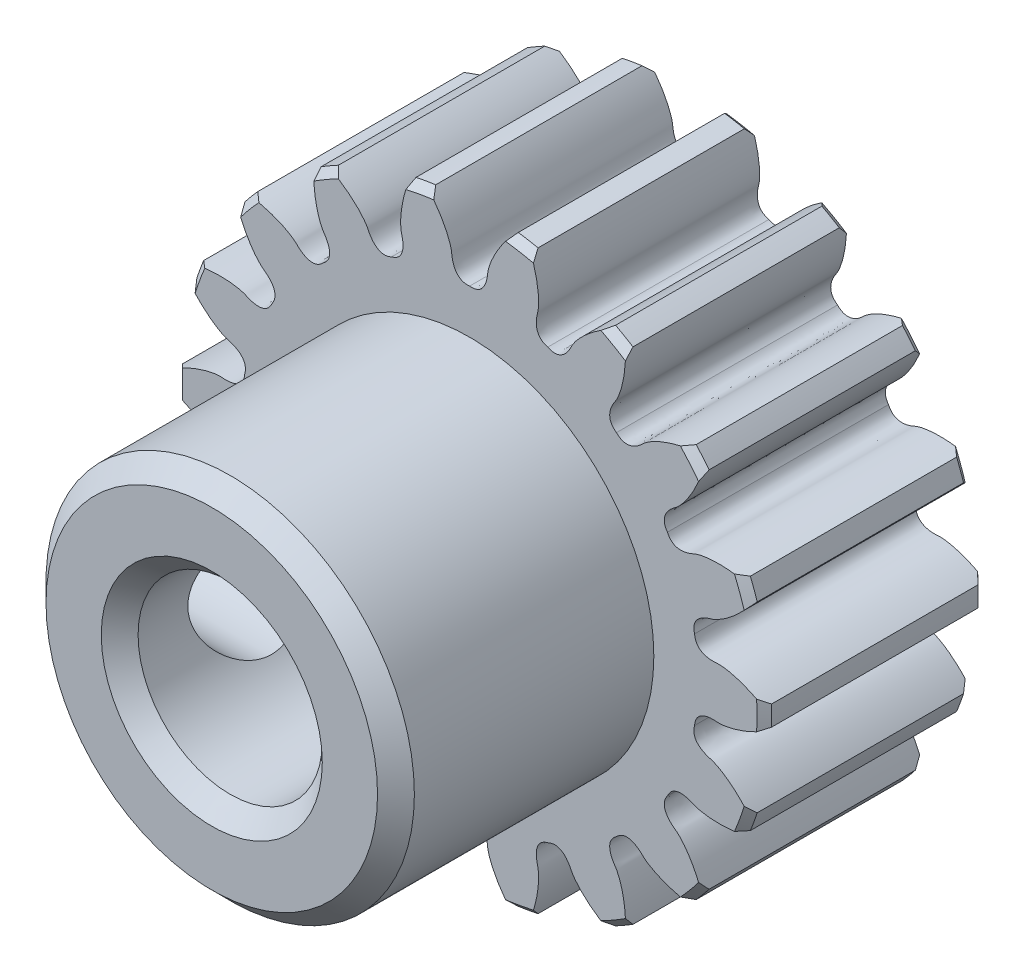
SolidWorks part; units mm, degrees
ref_plane "Front Plane" through (0, 0, 0) normal (0, 0, 1) x (1, 0, 0)
ref_plane "Top Plane" through (0, 0, 0) normal (0, 1, 0) x (1, 0, 0)
ref_plane "Right Plane" through (0, 0, 0) normal (1, 0, 0) x (0, 0, -1)
ref_axis "Ось вращения" through (0, 0, -4.277) along (0, 0, 1)
sketch "Gear-BaseSketch" plane through (0, 0, 0) normal (0, 0, 1) x (1, 0, 0)
  circle A0 centre (0, 0) radius 8
  dimension "D1" = 16
extrude "0.8 Module, 14,4000mm P.D." add sketch "Gear-BaseSketch" along normal mid plane 6
sketch "Tooth-Sketch; Backlash: 0,0000mm" plane through (0, 0, 0) normal (0, 0, 1) x (1, 0, 0)
  line L0 (0, 0) -> (0, 10.1487) construction
  arc A0 (-1.1887, 8.0004) -> (1.1887, 8.0004) centre (0, 0) cw
  spline S0 degree 3 poles (-1.1887, 8.0004) (-1.1086, 7.9105) (-0.9981, 7.7756) (-0.8682, 7.5934) (-0.7874, 7.4689) (-0.7187, 7.3521) (-0.6612, 7.2438) (-0.6139, 7.1448) (-0.5761, 7.0557) (-0.5467, 6.9771) (-0.5248, 6.9096) (-0.5092, 6.8537) (-0.499, 6.8097) (-0.4931, 6.7779) (-0.4902, 6.7588) (-0.4887, 6.7435) (-0.4868, 6.7196) (-0.4829, 6.6833) (-0.4745, 6.6262) (-0.4602, 6.5585) (-0.4361, 6.4818) (-0.4042, 6.4101) (-0.3617, 6.3426) (-0.3042, 6.2799) (-0.1904, 6.2022) (-0.0755, 6.1931) (0, 6.1994) knots 0 0 0 0 0.157962 0.228481 0.293358 0.352594 0.406188 0.454141 0.496452 0.533122 0.56415 0.589537 0.609282 0.623386 0.631848 0.634669 0.643503 0.663346 0.682539 0.719174 0.75397 0.787768 0.821855 0.858104 0.898741 1 1 1 1
  spline S1 degree 3 poles (1.1887, 8.0004) (1.1086, 7.9105) (0.9981, 7.7756) (0.8682, 7.5934) (0.7874, 7.4689) (0.7187, 7.3521) (0.6612, 7.2438) (0.6139, 7.1448) (0.5761, 7.0557) (0.5467, 6.9771) (0.5248, 6.9096) (0.5092, 6.8537) (0.499, 6.8097) (0.4931, 6.7779) (0.4902, 6.7588) (0.4887, 6.7435) (0.4868, 6.7196) (0.4829, 6.6833) (0.4745, 6.6262) (0.4602, 6.5585) (0.4361, 6.4818) (0.4042, 6.4101) (0.3617, 6.3426) (0.3042, 6.2799) (0.1904, 6.2022) (0.0755, 6.1931) (0, 6.1994) knots 0 0 0 0 0.157962 0.228481 0.293358 0.352594 0.406188 0.454141 0.496452 0.533122 0.56415 0.589537 0.609282 0.623386 0.631848 0.634669 0.643503 0.663346 0.682539 0.719174 0.75397 0.787768 0.821855 0.858104 0.898741 1 1 1 1
extrude "Tooth-Cut, Coarse Pitch Involute 20 deg" cut sketch "Tooth-Sketch; Backlash: 0,0000mm" against normal through all and the other way through all
chamfer "Фаска шестерни" distance 0.2 angle 45 2 edges at (0, -8, -3) (0, -8, 3)
pattern_circular "Tooth Pattern, 18 / 18" count 18 over 360 about axis through (0, 0, -4.277) along (0, 0, 1) of "Tooth-Cut, Coarse Pitch Involute 20 deg"
sketch "Sketch3" plane through (0, 0, 3) normal (0, 0, 1) x (1, 0, 0)
  circle A0 centre (0, 0) radius 5
  circle A1 centre (0, 0) radius 2.5
  dimension "D1" = 5
  dimension "D2" = 10
extrude "Хвостовик" add sketch "Sketch3" along normal blind 7
sketch "Sketch4" plane through (0, 0, -3) normal (0, 0, -1) x (-1, 0, 0)
  circle A0 centre (0, 0) radius 5
  dimension "D1" = 10
extrude "Вырез" cut sketch "Sketch4" against normal blind 3
sketch "Sketch5" plane through (0, 0, 3) normal (0, 0, 1) x (1, 0, 0)
  circle A0 centre (0, 0) radius 2.5
extrude "Сквозное" cut sketch "Sketch5" against normal blind 3
chamfer "Фаска" distance 0.5 angle 45 4 edges at (5, 0, 10) (2.5, 0, 10) (-5, 0, -3) (2.5, 0, 0)
ref_plane "Продольная" through (0, 0, 0) normal (1, 0, 0) x (0, 0, -1)
ref_plane "Касательная" through (-5, 0, 0) normal (-1, 0, 0) x (0, 0, 1)
sketch "Sketch6" plane through (-5, 0, 0) normal (-1, 0, 0) x (0, 0, 1)
  line L0 (-4.277, 0) -> (11.0141, 0) construction
  line L1 (10, -4.5) -> (10, 4.5) construction
  circle A0 centre (6.5, 0) radius 1.65
  dimension "D1" = 3.5
extrude "Резьба под установочный винт" cut sketch "Sketch6" against normal blind 4
cosmetic thread "Cosmetic Thread2" parameters "D2"=4
ref_axis "Крепежная ось" through (-1.7531, 0, 6.5) along (-1, 0, 0)
